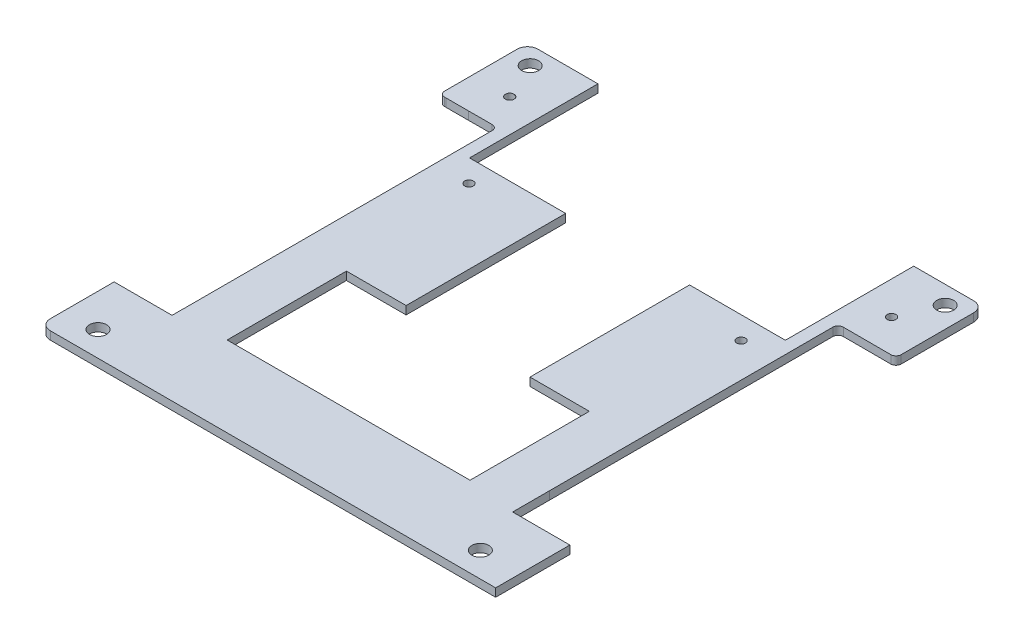
SolidWorks part; units mm, degrees
material "Copper"
ref_plane "Front Plane" through (0, 0, 0) normal (0, 0, 1) x (1, 0, 0)
ref_plane "Top Plane" through (0, 0, 0) normal (0, 1, 0) x (1, 0, 0)
ref_plane "Right Plane" through (0, 0, 0) normal (1, 0, 0) x (0, 0, -1)
sketch "Sketch1" plane through (0, 0, 0) normal (0, 1, 0) x (1, 0, 0)
  line L0 (-38.395, 30) -> (-42.73, 30)
  line L1 (-44, 31.27) -> (-44, 45)
  line L2 (42, 47) -> (30.435, 47)
  line L3 (44, 45) -> (44, 32)
  line L4 (44, 32) -> (44, 31.0156)
  line L5 (42.9984, 30.0156) -> (33.8256, 30.0304)
  line L6 (32.824, 29.0304) -> (32.824, -30.454)
  line L7 (-44, -38.977) -> (-44, -32.454)
  line L8 (-42, -47) -> (43.8497, -47)
  line L9 (-44, -45) -> (-44, -38.977)
  line L10 (-43, -31.454) -> (-36.1, -31.454)
  line L11 (43.8497, -37) -> (43.8497, -32.454)
  line L12 (42.8497, -31.454) -> (36.1, -31.454)
  line L13 (23.409, -31.5) -> (-23.409, -31.5)
  line L14 (-11.909, -8.5) -> (-23.409, -8.5)
  line L15 (30.435, 22.2554) -> (11.9708, 22.2554)
  line L16 (-11.909, -8.5) -> (-11.909, 22.2554)
  line L17 (30.435, 47) -> (30.435, 22.2554)
  line L18 (11.9708, 22.2554) -> (11.9708, -8.5)
  line L19 (-23.409, -31.5) -> (-23.409, -8.5)
  line L20 (11.9708, -8.5) -> (23.409, -8.5)
  line L21 (-36.1, -31.454) -> (-33.824, -31.454)
  line L22 (-32.824, -30.454) -> (-32.824, 29.0115)
  line L23 (-33.8265, 30.0115) -> (-38.395, 30)
  line L24 (-42.73, 30) -> (-43.011, 30.0031)
  line L25 (-44, 31.003) -> (-44, 31.27)
  line L28 (43.8497, -47) -> (43.8497, -37)
  line L33 (33.824, -31.454) -> (36.1, -31.454)
  line L34 (-23.409, 13.2954) -> (-23.409, -31.5) construction
  line L35 (23.409, -31.5) -> (23.409, -8.5)
  line L41 (-42, 47) -> (-30.435, 47)
  line L42 (-30.435, 47) -> (-30.435, 22.2554)
  line L43 (-30.435, 22.2554) -> (-11.909, 22.2554)
  circle A0 centre (40, 43.5) radius 1.6383
  circle A1 centre (-40, 43.5) radius 1.6383
  circle A2 centre (-37.6, -42.2) radius 1.6383
  circle A3 centre (36.1, -42.2) radius 1.6383
  circle A4 centre (-36.785, 36.35) radius 0.8382
  arc A5 (-42, 47) -> (-44, 45) centre (-42, 45) ccw
  arc A6 (44, 45) -> (42, 47) centre (42, 45) ccw
  circle A7 centre (-26.22, 17.9319) radius 0.8382
  circle A8 centre (26.22, 17.9319) radius 0.8382
  arc A9 (-43.011, 30.0031) -> (-44, 31.003) centre (-43, 31.003) cw
  arc A10 (-32.824, 29.0115) -> (-33.8265, 30.0115) centre (-33.824, 29.0115) ccw
  arc A11 (-44, -45) -> (-42, -47) centre (-42, -45) ccw
  arc A12 (44, 31.0156) -> (42.9984, 30.0156) centre (43, 31.0156) cw
  circle A13 centre (36.785, 36.368) radius 0.8382
  arc A14 (33.8256, 30.0304) -> (32.824, 29.0304) centre (33.824, 29.0304) ccw
  arc A15 (43.8497, -32.454) -> (42.8497, -31.454) centre (42.8497, -32.454) ccw
  arc A16 (32.824, -30.454) -> (33.824, -31.454) centre (33.824, -30.454) ccw
  arc A17 (-33.824, -31.454) -> (-32.824, -30.454) centre (-33.824, -30.454) ccw
  arc A18 (-44, -32.454) -> (-43, -31.454) centre (-43, -32.454) cw
  point P37 (-44, 30.014)
  point P48 (-32.824, 30.014)
  point P61 (44, 30.014)
  point P80 (32.824, 30.032)
  point P95 (32.824, -31.454)
  point P98 (-32.824, -31.454)
  dimension "D1" = 1
  dimension "D2" = 73.7
  dimension "D3" = 85.7
  dimension "D4" = 80
  dimension "D5" = 85.7
extrude "Boss-Extrude1" [suppressed] add sketch "Sketch1" along normal blind 1.575
extrude "Boss-Extrude2" add sketch "Sketch1<2>" along normal blind 1.575
sketch "Sketch1<2>" plane through (0, 0, 0) normal (0, 1, 0) x (1, 0, 0) same geometry as "Sketch1"
sketch "Sketch2" plane through (0, 1.575, 0) normal (0, 1, 0) x (1, 0, 0)
  line L1 (32.8227, -32.694) -> (46.9034, -32.694)
  line L2 (32.8227, -32.694) -> (32.8227, -25.5777)
  line L3 (32.8227, -25.5777) -> (46.9034, -25.5777)
  line L4 (46.9034, -32.694) -> (46.9034, -25.5777)
  line L5 (-47.8402, -23.2727) -> (-32.833, -23.2727)
  line L6 (-47.8402, -23.2727) -> (-47.8402, -32.694)
  line L7 (-47.8402, -32.694) -> (-32.833, -32.694)
  line L8 (-32.833, -23.2727) -> (-32.833, -32.694)
  dimension "D1" = 14.306
  dimension "D2" = 11.027
  dimension "D3" = 11.167
  dimension "D4" = 14.306
extrude "Cut-Extrude1" cut sketch "Sketch2" against normal through all
